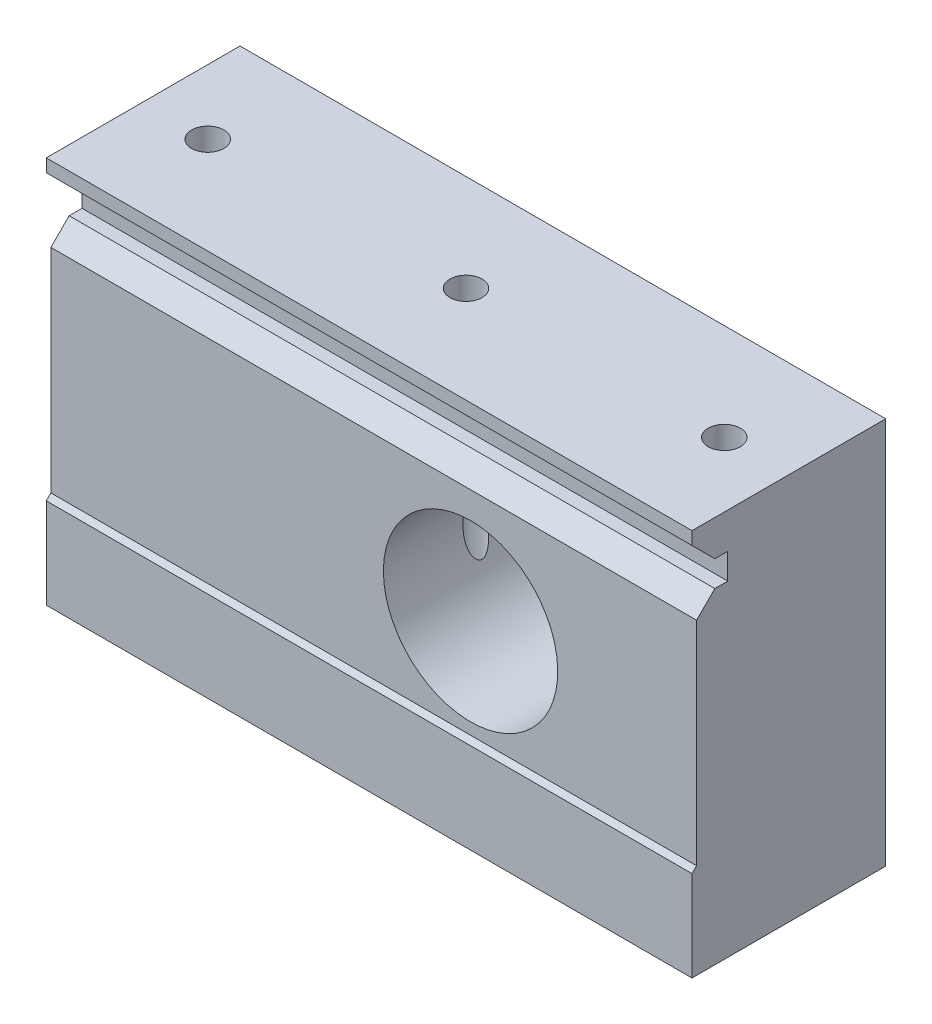
SolidWorks part; units mm, degrees
ref_plane "Front Plane" through (0, 0, 0) normal (0, 0, 1) x (1, 0, 0)
ref_plane "Top Plane" through (0, 0, 0) normal (0, 1, 0) x (1, 0, 0)
ref_plane "Right Plane" through (0, 0, 0) normal (1, 0, 0) x (0, 0, -1)
sketch "Sketch1" plane through (0, 0, 0) normal (0, 0, 1) x (1, 0, 0)
  line L1 (-47.9208, 29.5149) -> (52.0792, 29.5149)
  line L2 (-47.9208, 29.5149) -> (-47.9208, -30.4851)
  line L3 (-47.9208, -30.4851) -> (52.0792, -30.4851)
  line L4 (52.0792, 29.5149) -> (52.0792, -30.4851)
  dimension "D1" = 100
  dimension "D2" = 60
extrude "Boss-Extrude1" add sketch "Sketch1" along normal blind 30
sketch "Sketch3" plane through (-47.9208, 0, 0) normal (-1, 0, 0) x (0, 0, 1)
  line L10 (30, -30.4851) -> (30, -16.4851)
  line L11 (30, 29.5149) -> (30, -30.4851) construction
  line L12 (30, -16.4851) -> (29.2929, -15.778)
  line L13 (29.2929, -15.778) -> (29.2929, 17.1509)
  line L14 (29.2929, 17.1509) -> (26.4645, 19.9793)
  line L15 (26.4645, 19.9793) -> (24.4645, 19.9793)
  line L16 (24.4645, 19.9793) -> (24.4645, 23.9793)
  line L17 (24.4645, 23.9793) -> (26.4645, 23.9793)
  line L18 (26.4645, 23.9793) -> (30, 27.5149)
  line L19 (30, 27.5149) -> (30, 29.5149)
  line L20 (30, 29.5149) -> (35.631, 28.6016)
  line L21 (35.631, 28.6016) -> (37.1491, -26.2478)
  line L22 (37.1491, -26.2478) -> (30, -30.4851)
  dimension "D1" = 2
  dimension "D2" = 4
  dimension "D3" = 5
  dimension "D4" = 4
  dimension "D5" = 2
  dimension "D6" = 135
  dimension "D7" = 14
extrude "Cut-Extrude1" cut sketch "Sketch3" against normal blind 110
sketch "Эскиз1" plane through (0, 29.5149, 0) normal (0, 1, 0) x (1, 0, 0)
  line L0 (52.0792, 0) -> (-47.9208, 0) construction
  line L1 (52.0792, -30) -> (52.0792, 0) construction
  circle A0 centre (42.0792, -15) radius 2.4933
  dimension "D2" = 10
  dimension "D1" = 15
extrude "Вырез-Вытянуть1" cut sketch "Эскиз1" against normal blind 100
pattern_linear "Линейный массив1" count 3 spacing 40 along (-1, 0, 0) of "Вырез-Вытянуть1"
sketch "Эскиз2" plane through (0, 0, 0) normal (0, 0, -1) x (-1, 0, 0)
  line L0 (-52.0792, 29.5149) -> (47.9208, 29.5149) construction
  line L1 (-52.0792, -30.4851) -> (-52.0792, 29.5149) construction
  circle A0 centre (-17.0792, -0.4851) radius 13.5
  dimension "D1" = 30
  dimension "D2" = 35
extrude "Вырез-Вытянуть2" cut sketch "Эскиз2" against normal blind 100
